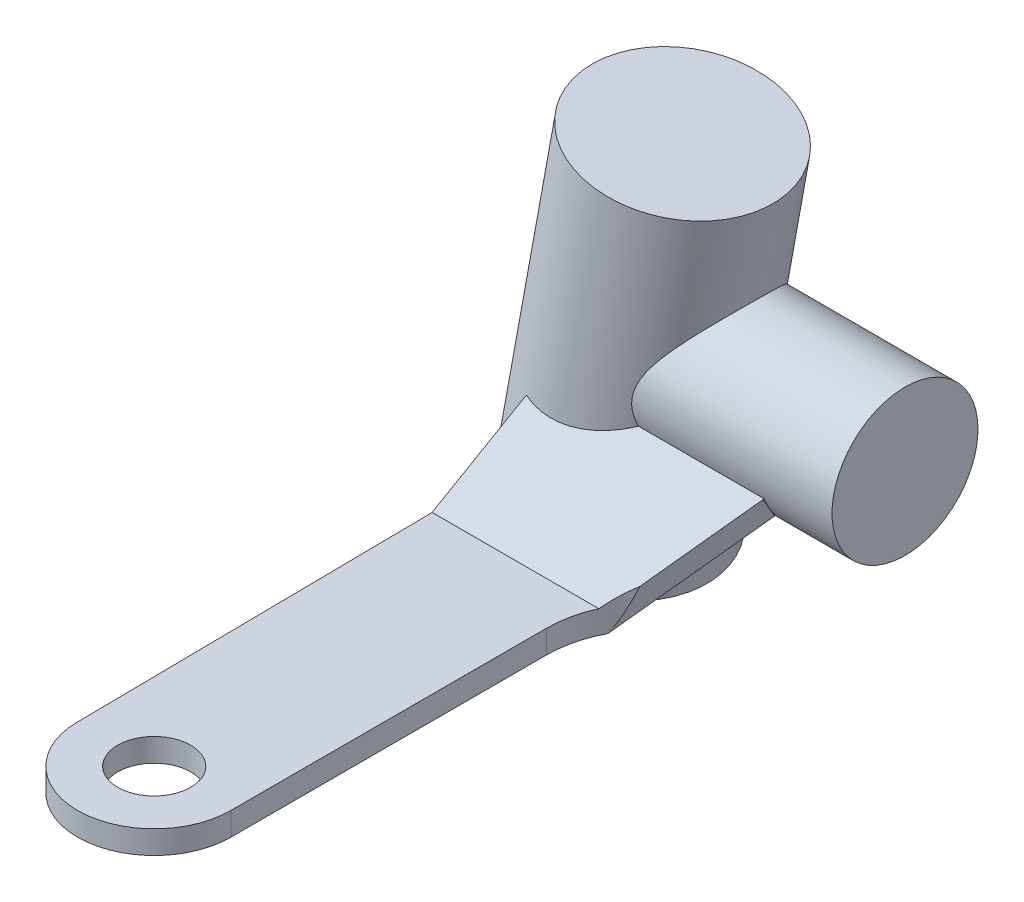
SolidWorks part; units mm, degrees
ref_plane "Front Plane" through (0, 0, 0) normal (0, 0, 1) x (1, 0, 0)
ref_plane "Top Plane" through (0, 0, 0) normal (0, 1, 0) x (1, 0, 0)
ref_plane "Right Plane" through (0, 0, 0) normal (1, 0, 0) x (0, 0, -1)
sketch "Sketch1" plane through (0, 0, 0) normal (1, 0, 0) x (0, 0, -1)
  circle A0 centre (0, 0) radius 10
  dimension "D1" = 20
extrude "Boss-Extrude1" add sketch "Sketch1" along normal blind 25 and the other way blind 10
ref_point "Point1"
ref_plane "Plane1" through (-10, 0, 0) normal (0.1736, 0.9848, -0.0071) x (0.9848, -0.1737, 0)
sketch "Sketch2" plane through (-10, 0, 0) normal (0.1736, 0.9848, -0.0071) x (0.9848, -0.1737, 0)
  circle A0 centre (0, 0) radius 12.5
  dimension "D1" = 25
extrude "Boss-Extrude2" add sketch "Sketch2" along normal mid plane 50
ref_plane "Plane2" through (-9.6985, 1.7101, -0.0123) normal (-0.9848, 0.1736, -0.0013) x (0.1736, 0.9848, -0.0071)
sketch "Sketch5" plane through (0, 0, 0) normal (1, 0, 0) x (0, 0, -1)
  line L0 (0.7937, -1.3748) -> (-0.7937, 1.3748)
  line L1 (-0.7937, 1.3748) -> (-25.5297, -12.9065)
  line L2 (-25.5297, -12.9065) -> (-23.9422, -15.6561)
  line L3 (-23.9422, -15.6561) -> (0.7937, -1.3748)
  line L4 (0, 0) -> (50.9555, 0) construction
  line L6 (-12.3221, 24.7097) -> (-12.6773, -24.5294) construction
  point P8 (-12.5393, -5.4065)
  dimension "D1" = 3.175
  dimension "D2" = 30
  dimension "D3" = 15
extrude "Boss-Extrude3" add sketch "Sketch5" along normal blind 15 and the other way blind 15
sketch "Sketch6" plane through (0, -1.3748, -0.7937) normal (0, -0.866, -0.5) x (1, 0, 0)
  line L0 (15, 28.5626) -> (15, 10)
  line L1 (15, 28.5626) -> (15, 9.8732) construction
  line L2 (15, 10) -> (8.2438, 28.5626)
  line L3 (-15, 28.5626) -> (15, 28.5626) construction
  line L4 (8.2438, 28.5626) -> (15, 28.5626)
  dimension "D1" = 20
extrude "Cut-Extrude1" cut sketch "Sketch6" against normal blind 10
ref_plane "Plane5" through (0, -15.6561, 0) normal (0, -1, 0) x (1, 0, 0)
sketch "Sketch7" plane through (0, -15.6561, 0) normal (0, -1, 0) x (1, 0, 0)
  line L0 (-15, 23.9422) -> (-14.421, 73.9422)
  line L1 (6.579, 73.9422) -> (6.579, 30.6823)
  line L2 (8.2438, 23.9422) -> (-15, 23.9422)
  circle A0 centre (-3.921, 73.9422) radius 10.5
  arc A1 (6.579, 30.6823) -> (8.2438, 23.9422) centre (21.0562, 30.6823) ccw
  dimension "D1" = 21
  dimension "D2" = 50
extrude "Boss-Extrude4" add sketch "Sketch7" against normal blind 3.175 contours A1 L1 A0 L0 L2 | A0 region at (-4.0491, -15.6561, 44.7369) region at (-3.921, -15.6561, 73.9422)
sketch "Sketch9" plane through (0, -15.6561, 0) normal (0, -1, 0) x (1, 0, 0)
  line L0 (17.2968, 44.6628) -> (24.8156, 16.7018)
  arc A0 (24.8156, 16.7018) -> (17.2968, 44.6628) centre (21.0562, 30.6823) cw
  arc A1 (6.579, 30.6823) -> (8.2438, 23.9422) centre (21.0562, 30.6823) ccw construction
extrude "Cut-Extrude2" cut sketch "Sketch9" against normal blind 10
sketch "Sketch11" plane through (0, -12.4811, 0) normal (0, 1, 0) x (1, 0, 0)
  circle A0 centre (-3.921, -73.9422) radius 5
  arc A4 (-14.421, -73.9422) -> (6.579, -73.9422) centre (-3.921, -73.9422) ccw construction
extrude "Cut-Extrude6" cut sketch "Sketch11" against normal blind 10
sketch "Sketch12" plane through (0, -12.4811, 0) normal (0, 1, 0) x (1, 0, 0)
  point P0 (-3.921, -73.9422)
